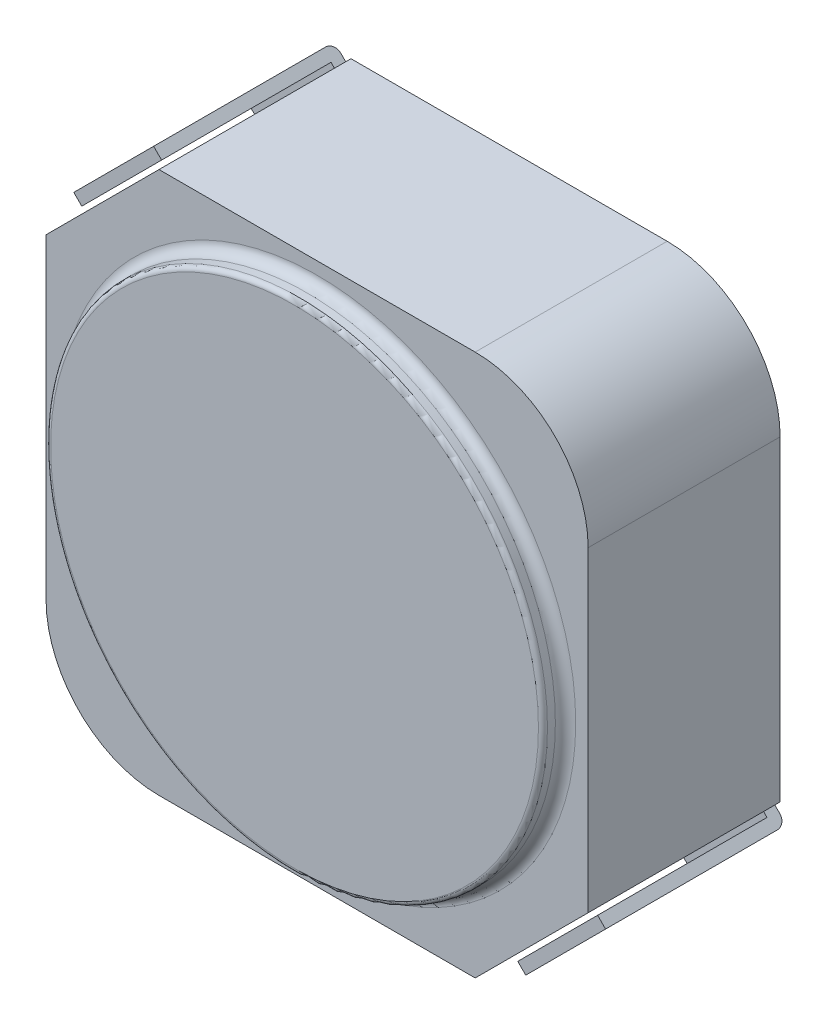
SolidWorks part; units mm, degrees
ref_plane "Спереди" through (0, 0, 0) normal (0, 0, 1) x (1, 0, 0)
ref_plane "Сверху" through (0, 0, 0) normal (0, 1, 0) x (1, 0, 0)
ref_plane "Справа" through (0, 0, 0) normal (1, 0, 0) x (0, 0, -1)
sketch "Эскиз2" plane through (0, 0, 0) normal (0, 0, 1) x (1, 0, 0)
  line L1 (-1.4, 2.4) -> (1.4, 2.4)
  line L2 (-2.4, 1.4) -> (-2.4, -1.4)
  line L3 (-1.4, -2.4) -> (1.4, -2.4)
  line L4 (2.4, 1.4) -> (2.4, -1.4)
  line L5 (-2.4, -2.4) -> (2.4, -2.4) construction
  line L6 (-2.4, 1.4) -> (-1.4, 2.4)
  line L7 (-2.4, -2.4) -> (-2.4, 2.4) construction
  line L8 (-2.4, 2.4) -> (2.4, 2.4) construction
  line L9 (1.4, -2.4) -> (2.4, -1.4)
  line L10 (2.4, -2.4) -> (2.4, 2.4) construction
  line L11 (-2.4, -2.4) -> (2.4, 2.4) construction
  line L12 (-2.4, 2.4) -> (2.4, -2.4) construction
  arc A0 (-2.4, -1.4) -> (-1.4, -2.4) centre (-1.4, -1.4) ccw
  arc A1 (2.4, 1.4) -> (1.4, 2.4) centre (1.4, 1.4) ccw
  point P0 (-2.4, 2.4)
  point P1 (2.4, -2.4)
  point P8 (0, 0)
  point P15 (0, 0)
  dimension "D1" = 1
  dimension "D2" = 1
  dimension "D4" = 4.8
extrude "Вытянуть1" add sketch "Эскиз2" along normal blind 1.7 from offset 0.1
sketch "Эскиз6" plane through (0, 0, 0) normal (0, 0, 1) x (1, 0, 0)
  circle A1 centre (0, 0) radius 2
extrude "Вытянуть5" cut sketch "Эскиз6" along normal blind 0.3
sketch "Эскиз8" plane through (0, 0, 0) normal (0, 0, 1) x (1, 0, 0)
  circle A0 centre (0, 0) radius 1.7
extrude "Вытянуть9" add sketch "Эскиз8" along normal blind 0.25 from offset 0.1
sketch "Эскиз9" plane through (0, 0, 0) normal (0, 0, 1) x (1, 0, 0)
  circle A0 centre (0, 0) radius 2.2
extrude "Бобышка-Вытянуть1" add sketch "Эскиз9" along normal blind 0.5 from offset 1.5
fillet "Скругление2" radius 0.09 1 edges at (2.2, 0, 1.8)
fillet "Скругление3" radius 0.04 1 edges at (2.2, 0, 2)
sketch "Эскиз10" plane through (0, 0, 0) normal (0, 0, 1) x (1, 0, 0)
  line L0 (2.25, 0.75) -> (1.5, 0.75)
  line L1 (-2.25, 0.75) -> (-1.5, 0.75)
  line L2 (1.5, 2.25) -> (-1.55, 2.25)
  line L3 (2.25, 0.75) -> (2.25, 1.5)
  line L4 (-2.25, 0.75) -> (-2.25, 1.55)
  line L5 (1.5, 2.25) -> (2.25, 1.5)
  line L6 (-1.55, 2.25) -> (-2.25, 1.55)
  line L7 (-2.25, -0.75) -> (-1.5, -0.75)
  line L8 (2.25, -0.75) -> (1.5, -0.75)
  line L9 (-1.5, -2.25) -> (1.55, -2.25)
  line L10 (-2.25, -0.75) -> (-2.25, -1.5)
  line L11 (2.25, -0.75) -> (2.25, -1.55)
  line L12 (-1.5, -2.25) -> (-2.25, -1.5)
  line L13 (1.55, -2.25) -> (2.25, -1.55)
  arc A0 (1.5, 0.75) -> (-1.5, 0.75) centre (0, 0) ccw
  arc A1 (-1.5, -0.75) -> (1.5, -0.75) centre (0, 0) ccw
  dimension "D1" = 2
extrude "Бобышка-Вытянуть2" add sketch "Эскиз10" along normal blind 0.1
ref_axis "Ось1" through (0, 0, -0.15) along (0, 0, 1)
ref_plane "Плоскость2" through (0, 0, 0) normal (-0.7071, 0.7071, 0) x (-0.7071, -0.7071, 0)
sketch "Эскиз11" plane through (0, 0, 0) normal (0.7071, -0.7071, 0) x (0, 0, -1)
  line L1 (-1.6, 0.5) -> (-0.1, 0.5)
  line L2 (-1.6, 0.5) -> (-1.6, -0.5)
  line L3 (-1.6, -0.5) -> (-0.1, -0.5)
  line L4 (-0.1, 0.5) -> (-0.1, -0.5)
extrude "Бобышка-Вытянуть3" add sketch "Эскиз11" along normal blind 0.1 from offset 2.73 separate body
extrude "Бобышка-Вытянуть4" add sketch "Эскиз11<2>" against normal blind 0.1 from offset 2.73 separate body offset against normal yes
sketch "Эскиз11<2>" plane through (0, 0, 0) normal (0.7071, -0.7071, 0) x (0, 0, -1) same geometry as "Эскиз11"
ref_plane "Плоскость3" through (0, 0, 0) normal (-0.7071, -0.7071, 0) x (0.7071, -0.7071, 0)
sketch "Эскиз12" plane through (0, 0, 0) normal (-0.7071, -0.7071, 0) x (0.7071, -0.7071, 0)
  line L0 (2.83, 0.15) -> (2.83, 0.08)
  line L1 (2.75, 0) -> (2.6, 0)
  line L2 (2.6, 0.1) -> (2.73, 0.1)
  line L3 (2.73, 0.1) -> (2.73, 0.15)
  line L4 (2.73, 0.15) -> (2.83, 0.15)
  line L5 (2.6, 0.1) -> (2.6, 0)
  line L6 (0, -0.6039) -> (0, -0.4596) construction
  line L7 (-2.6, 0.1) -> (-2.6, 0)
  line L8 (-2.73, 0.15) -> (-2.83, 0.15)
  line L9 (-2.73, 0.1) -> (-2.73, 0.15)
  line L10 (-2.6, 0.1) -> (-2.73, 0.1)
  line L11 (-2.75, 0) -> (-2.6, 0)
  line L12 (-2.83, 0.15) -> (-2.83, 0.08)
  arc A0 (2.83, 0.08) -> (2.75, 0) centre (2.75, 0.08) cw
  arc A1 (-2.83, 0.08) -> (-2.75, 0) centre (-2.75, 0.08) ccw
  dimension "D1" = 0.08
extrude "Бобышка-Вытянуть5" add sketch "Эскиз12" against normal blind 1 from offset 0.5
